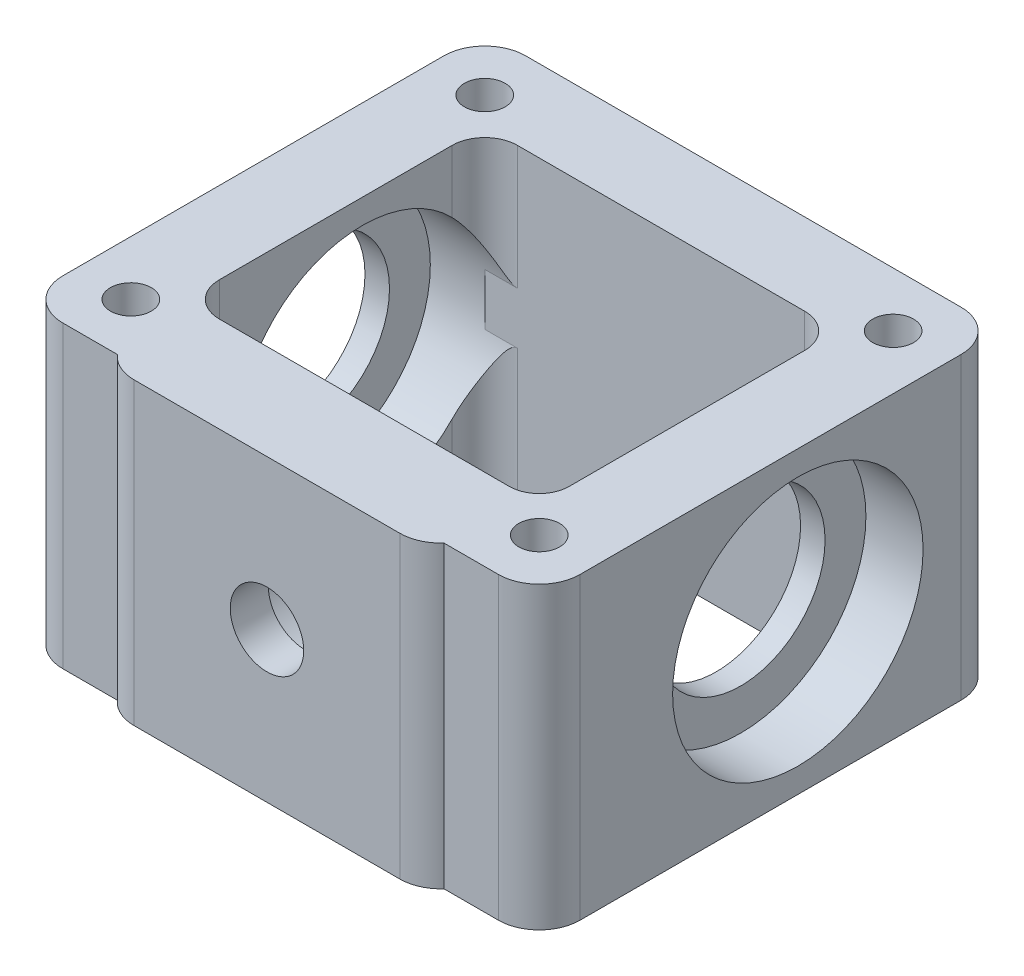
SolidWorks part; units mm, degrees
ref_plane "Front" through (0, 0, 0) normal (0, 0, 1) x (1, 0, 0)
ref_plane "Top" through (0, 0, 0) normal (0, 1, 0) x (1, 0, 0)
ref_plane "Right" through (0, 0, 0) normal (1, 0, 0) x (0, 0, -1)
sketch "Sketch3" plane through (0, 0, 0) normal (0, 1, 0) x (1, 0, 0)
  line L0 (6, -6) -> (32, -6)
  line L1 (0, 0) -> (38, 0)
  line L2 (0, 0) -> (0, -34)
  line L3 (0, -34) -> (38, -34)
  line L4 (38, 0) -> (38, -34)
  line L5 (32, -6) -> (32, -28)
  line L6 (6, -28) -> (32, -28)
  line L7 (6, -6) -> (6, -28)
  dimension "D1" = 38
  dimension "D2" = 34
  dimension "D3" = 6
extrude "Boss-Extrude1" add sketch "Sketch3" along normal blind 22
sketch "Sketch4" plane through (0, 0, 34) normal (0, 0, 1) x (1, 0, 0)
  line L0 (0, 0) -> (38, 0) construction
  line L1 (31, 0) -> (7, 0)
  line L2 (31, 0) -> (31, 22)
  line L3 (31, 22) -> (7, 22)
  line L4 (7, 0) -> (7, 22)
  line L5 (0, 22) -> (38, 22) construction
  dimension "D1" = 24
  dimension "D2" = 7
extrude "Boss-Extrude2" add sketch "Sketch4" along normal blind 1
sketch "Sketch5" plane through (0, 0, 35) normal (0, 0, 1) x (1, 0, 0)
  line L0 (31, 0) -> (31, 22) construction
  line L1 (7, 0) -> (31, 0) construction
  circle A0 centre (19, 11) radius 2.7
  dimension "D3" = 5.4
  dimension "D1" = 12
  dimension "D2" = 11
extrude "Cut-Extrude1" cut sketch "Sketch5" against normal blind 12
sketch "Sketch7" plane through (0, 0, 28) normal (0, 0, -1) x (-1, 0, 0)
  circle A0 centre (-19, 11) radius 5.7
  dimension "D1" = 11.4
extrude "Cut-Extrude3" cut sketch "Sketch7" against normal blind 4.2
sketch "Sketch8" plane through (38, 0, 0) normal (1, 0, 0) x (0, 0, -1)
  line L0 (0, 22) -> (0, 0) construction
  line L1 (-34, 0) -> (0, 0) construction
  circle A0 centre (-15, 11) radius 6.2
  dimension "D1" = 12.4
  dimension "D2" = 15
  dimension "D3" = 11
extrude "Cut-Extrude4" cut sketch "Sketch8" against normal through all
sketch "Sketch9" plane through (6, 0, 0) normal (1, 0, 0) x (0, 0, -1)
  circle A0 centre (-15, 11) radius 9.2
  dimension "D1" = 18.4
extrude "Cut-Extrude5" cut sketch "Sketch9" against normal blind 4.2
sketch "Sketch10" plane through (38, 0, 0) normal (1, 0, 0) x (0, 0, -1)
  circle A0 centre (-15, 11) radius 9.2
  dimension "D1" = 18.4
extrude "Cut-Extrude6" cut sketch "Sketch10" against normal blind 4.2
sketch "Sketch15" plane through (0, 0, 0) normal (0, -1, 0) x (-1, 0, 0)
  line L0 (0, 0) -> (0, -34) construction
  line L1 (0, -34) -> (-7, -34) construction
  circle A0 centre (-4, -30) radius 1.5
  circle A1 centre (-34, -30) radius 1.5
  circle A2 centre (-34, -4) radius 1.5
  circle A3 centre (-4, -4) radius 1.5
  dimension "D1" = 3
  dimension "D2" = 4
  dimension "D3" = 4
  dimension "D4" = 2
  dimension "D5" = 2
extrude "Cut-Extrude7" cut sketch "Sketch15" against normal through all
fillet "Fillet1" radius 3 6 edges at (38, 11, 0) (7, 11, 35) (0, 11, 34) (0, 11, 0) (31, 11, 35) (38, 11, 34)
fillet "Fillet3" radius 2.5 2 edges at (32, 11, 6) (6, 11, 28)
fillet "Fillet4" radius 2.2 1 edges at (32, 11, 28)
fillet "Fillet5" radius 2.4 2 edges at (6, 4.5461, 6) (6, 17.4539, 6)
